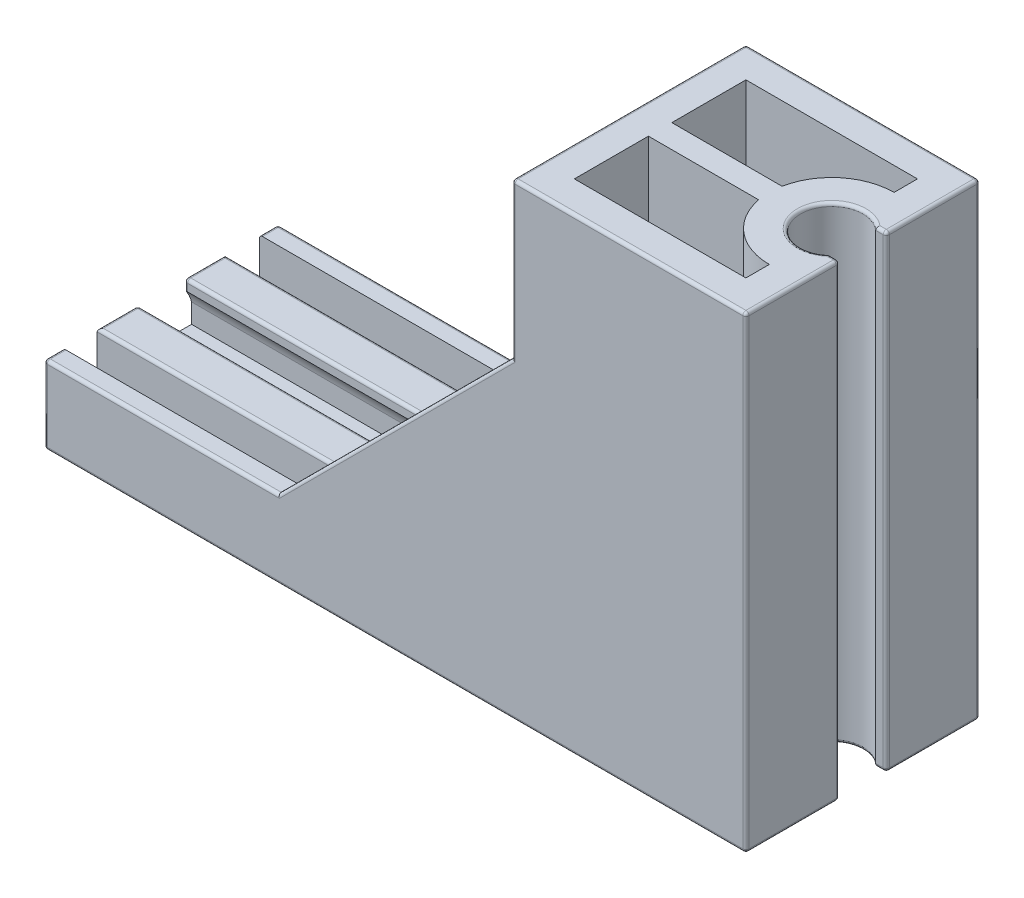
SolidWorks part; units mm, degrees
ref_plane "前视基准面" through (0, 0, 0) normal (0, 0, 1) x (1, 0, 0)
ref_plane "上视基准面" through (0, 0, 0) normal (0, 1, 0) x (1, 0, 0)
ref_plane "右视基准面" through (0, 0, 0) normal (1, 0, 0) x (0, 0, -1)
sketch "草图1" plane through (0, 0, 0) normal (0, 1, 0) x (1, 0, 0)
  line L0 (7.5, -7.5) -> (7.5, 7.5)
  line L1 (7.5, -7.5) -> (-7.5, -7.5)
  line L2 (7.5, 7.5) -> (-7.5, 7.5)
  line L3 (-7.5, -7.5) -> (-7.5, 7.5)
  line L4 (7.5, -7.5) -> (-7.5, 7.5) construction
  line L5 (7.5, 7.5) -> (-7.5, -7.5) construction
  point P1 (0, 0)
  dimension "D1" = 15
  dimension "D2" = 15
extrude "凸台-拉伸1" add sketch "草图1" along normal blind 30
sketch "草图2" plane through (0, 30, 0) normal (0, 1, 0) x (1, 0, 0)
  line L0 (7.5, 0) -> (5.5, 0) construction
  line L1 (7.5, -7.5) -> (7.5, 7.5) construction
  line L2 (7.5, -1.5) -> (7.5, 1.5)
  line L3 (7.5, 1.5) -> (6.8229, 1.5)
  line L4 (7.5, -1.5) -> (6.8229, -1.5)
  arc A0 (6.8229, 1.5) -> (6.8229, -1.5) centre (5.5, 0) ccw
  dimension "D3" = 2
  dimension "D1" = 2
  dimension "D2" = 1.5
extrude "切除-拉伸1" cut sketch "草图2" against normal through all
sketch "草图3" plane through (-7.5, 0, 0) normal (-1, 0, 0) x (0, 0, 1)
  line L0 (-7.5, 0) -> (7.5, 0)
  line L1 (-7.5, 0) -> (-7.5, 5)
  line L2 (7.5, 0) -> (7.5, 5)
  line L3 (-7.5, 5) -> (7.5, 5)
  dimension "D1" = 5
extrude "凸台-拉伸2" add sketch "草图3" along normal blind 30
sketch "草图4" plane through (-37.5, 0, 0) normal (-1, 0, 0) x (0, 0, 1)
  line L0 (0, 5) -> (0, 3) construction
  line L1 (7.5, 5) -> (-7.5, 5) construction
  line L2 (-1.5, 5) -> (1.5, 5)
  line L3 (7.5, 5) -> (-7.5, 5) construction
  line L4 (1.5, 5) -> (1.5, 4.3229)
  line L5 (0, 3) -> (0, 2.2) construction
  line L6 (-1.95, 2.2) -> (1.95, 2.2)
  line L7 (1.95, 2.2) -> (1.95, 3.4444)
  line L8 (-1.95, 2.2) -> (-1.95, 3.4444)
  line L9 (-1.5, 5) -> (-1.5, 4.3229)
  line L10 (4.1, 2.2) -> (6.3, 2.2)
  line L12 (7.5, 5) -> (6.3, 5) construction
  line L13 (6.3, 5) -> (6.3, 2.2)
  line L14 (6.3, 5) -> (4.1, 5)
  line L15 (4.1, 5) -> (4.1, 2.2)
  line L16 (-4.1, 2.2) -> (-6.3, 2.2)
  line L17 (-6.3, 5) -> (-6.3, 2.2)
  line L18 (-4.1, 5) -> (-4.1, 2.2)
  line L19 (-6.3, 5) -> (-4.1, 5)
  arc A0 (1.95, 3.4444) -> (1.5, 4.3229) centre (0, 3) ccw
  arc A1 (-1.95, 3.4444) -> (-1.5, 4.3229) centre (0, 3) cw
  dimension "D1" = 2
  dimension "D2" = 1.5
  dimension "D3" = 0.8
  dimension "D4" = 1.95
  dimension "D5" = 1.2
  dimension "D6" = 2.2
  dimension "D7" = 2.8
extrude "切除-拉伸2" cut sketch "草图4" against normal blind 30
sketch "草图5" plane through (0, 30, 0) normal (0, 1, 0) x (1, 0, 0)
  line L0 (5.5, -5.5) -> (5.5, -4)
  line L1 (5.5, -4) -> (5.5, -4)
  line L2 (5.5, 4) -> (5.5, 4)
  line L3 (5.5, 4) -> (5.5, 5.5)
  line L4 (5.5, 5.5) -> (-5.5, 5.5)
  line L5 (-5.5, 5.5) -> (-5.5, 0.75)
  line L6 (-5.5, -5.5) -> (5.5, -5.5)
  line L7 (7.5, -7.5) -> (7.5, -1.5)
  line L8 (7.5, -1.5) -> (6.8229, -1.5)
  line L9 (6.8229, 1.5) -> (7.5, 1.5)
  line L10 (7.5, 1.5) -> (7.5, 7.5)
  line L11 (7.5, 7.5) -> (-7.5, 7.5)
  line L12 (-7.5, 7.5) -> (-7.5, -7.5)
  line L13 (-7.5, -7.5) -> (7.5, -7.5)
  line L14 (7.5, -7.5) -> (7.5, -1.5) construction
  line L15 (7.5, -1.5) -> (6.8229, -1.5) construction
  line L16 (6.8229, 1.5) -> (7.5, 1.5) construction
  line L17 (7.5, 1.5) -> (7.5, 7.5) construction
  line L18 (7.5, 7.5) -> (-7.5, 7.5) construction
  line L19 (-7.5, 7.5) -> (-7.5, -7.5) construction
  line L20 (-7.5, -7.5) -> (7.5, -7.5) construction
  line L21 (-5.5, -0.753) -> (-5.5, -5.5)
  line L22 (1.5715, -0.753) -> (-5.5, -0.753)
  line L24 (-5.5, 5.5) -> (-5.5, -5.5) construction
  line L25 (1.5709, 0.75) -> (-5.5, 0.75)
  arc A0 (5.5, 4) -> (1.5709, 0.75) centre (5.5, 0) ccw
  arc A1 (6.8229, 1.5) -> (6.8229, -1.5) centre (5.5, 0) ccw
  arc A2 (6.8229, 1.5) -> (6.8229, -1.5) centre (5.5, 0) ccw construction
  arc A3 (1.5715, -0.753) -> (5.5, -4) centre (5.5, 0) ccw
  arc A5 (5.5, 4) -> (5.5, -4) centre (5.5, 0) ccw construction
  dimension "D3" = 0.75
  dimension "D4" = 0.753
  dimension "D5" = 7.0709
  dimension "D6" = 7.0715
  dimension "D1" = 0
  dimension "D2" = 2
extrude "切除-拉伸3" cut sketch "草图5" against normal blind 28.5
sketch "草图6" plane through (0, 0, 0) normal (0, 0, 1) x (1, 0, 0)
  line L0 (-37.5, 0) -> (-30, 0) construction
  line L1 (-37.5, 0) -> (7.5, 0) construction
  line L2 (-30, 0) -> (-30, -2) construction
  line L3 (-31.5, 0) -> (-28.5, 0)
  line L4 (-28.5, 0) -> (-28.5, -0.6771)
  line L5 (-30, -2) -> (-30, -2.5) construction
  line L6 (-31.95, -2.5) -> (-28.05, -2.5)
  line L7 (-28.05, -2.5) -> (-28.05, -1.5556)
  line L8 (-31.95, -2.5) -> (-31.95, -1.5556)
  line L9 (-31.5, 0) -> (-31.5, -0.6771)
  arc A0 (-28.05, -1.5556) -> (-28.5, -0.6771) centre (-30, -2) ccw
  arc A1 (-31.95, -1.5556) -> (-31.5, -0.6771) centre (-30, -2) cw
  dimension "D6" = 2
  dimension "D1" = 7.5
  dimension "D2" = 2
  dimension "D3" = 1.5
  dimension "D4" = 0.5
  dimension "D5" = 1.95
extrude "凸台-拉伸3" add sketch "草图6" along normal blind 3 and the other way blind 3
sketch "草图7" plane through (-37.5, 0, 0) normal (-1, 0, 0) x (0, 0, 1)
  line L0 (0, 0) -> (0, -2) construction
  line L1 (0, -2) -> (0, -2.5) construction
  line L2 (-3, -2.5) -> (3, -2.5) construction
  line L3 (3, -2.5) -> (1.95, -2.5)
  line L4 (-1.5, 0) -> (-1.5, -0.6771)
  line L5 (3, -2.5) -> (3, 0)
  line L6 (-1.95, -2.5) -> (-1.95, -1.5556)
  line L7 (1.95, -2.5) -> (1.95, -1.5556)
  line L8 (1.5, 0) -> (1.5, -0.6771)
  line L9 (-3, -2.5) -> (-3, 0)
  line L10 (3, 0) -> (1.5, 0)
  line L11 (-1.5, 0) -> (-3, 0)
  line L12 (-1.95, -2.5) -> (-3, -2.5)
  arc A0 (-1.5, -0.6771) -> (-1.95, -1.5556) centre (0, -2) ccw
  arc A1 (1.5, -0.6771) -> (1.95, -1.5556) centre (0, -2) cw
  dimension "D1" = 2
  dimension "D2" = 1.5
  dimension "D3" = 1.95
  dimension "D4" = 2.5
extrude "切除-拉伸4" cut sketch "草图7" against normal blind 15
fillet "圆角1" radius 0.1 4 edges at (-30, -2.5, 1.95) (-28.05, -2.5, 0) (-30, -2.5, -1.95) (-31.95, -2.5, 0)
pattern_linear "阵列(线性)1" count 3 spacing 15 along (1, 0, 0) of "圆角1", "切除-拉伸4", "凸台-拉伸3"
sketch "草图8" plane through (0, 0, 7.5) normal (0, 0, 1) x (1, 0, 0)
  line L0 (-7.5, 5) -> (-7.5, 20)
  line L1 (-7.5, 30) -> (-7.5, 5) construction
  line L2 (-7.5, 20) -> (-22.5, 5)
  line L3 (-37.5, 5) -> (-7.5, 5) construction
  line L4 (-22.5, 5) -> (-7.5, 5)
  dimension "D1" = 15
  dimension "D2" = 15
extrude "凸台-拉伸4" add sketch "草图8" against normal blind 1.2
mirror "镜向1" about plane through (0, 0, 0) normal (0, 0, 1) of "凸台-拉伸4"
fillet "圆角3" radius 0.2 2 edges at (7.5, 15, 1.5) (7.5, 15, -1.5)
fillet "圆角4" radius 0.2 10 edges at (0, 30, -7.5) (7.5, 30, -4.6) (7.4414, 30, -1.5586) (7.0614, 30, -1.5) (3.5, 30, 0) (7.0614, 30, 1.5) (7.4414, 30, 1.5586) (7.5, 30, 4.6) (0, 30, 7.5) (-7.5, 30, 0)
fillet "圆角5" radius 0.2 14 edges at (7.4414, 29.9414, -7.4414) (7.4414, 29.9414, 7.4414) (-37.5, 0, 0) (-15, 0, 7.5) (7.4414, 0, 1.5586) (7.0614, 0, 1.5) (3.5, 0, 0) (7.0614, 0, -1.5) (7.4414, 0, -1.5586) (-15, 0, -7.5) (7.5, 14.9, -7.5) (7.5, 0, -4.6) (7.5, 0, 4.6) (7.5, 14.9, 7.5)
fillet "圆角6" radius 0.2 12 edges at (-7.4414, 29.9414, 7.4414) (-37.4414, 0.0586, 7.4414) (-37.4414, 0.0586, -7.4414) (-7.4414, 29.9414, -7.4414) (-15, 12.5, 7.5) (-37.5, 2.6, 7.5) (-37.5, 2.6, -7.5) (-15, 12.5, -7.5)
fillet "圆角7" radius 0.2 8 edges at (-37.4414, 4.9414, 7.4414) (-37.4414, 4.9414, -7.4414) (-22.5, 5, -4.1) (-22.5, 5, 4.1) (-37.5, 5, 6.8) (-37.5, 5, 2.8) (-37.5, 5, -2.8) (-37.5, 5, -6.8)
fillet "圆角8" radius 0.2 6 edges at (-37.5, 4.5614, 1.5) (-37.4414, 4.9414, 1.5) (-37.5, 4.5614, -1.5) (-37.4414, 4.9414, -1.5) (-22.4, 5, 1.5) (-22.4, 5, -1.5)
